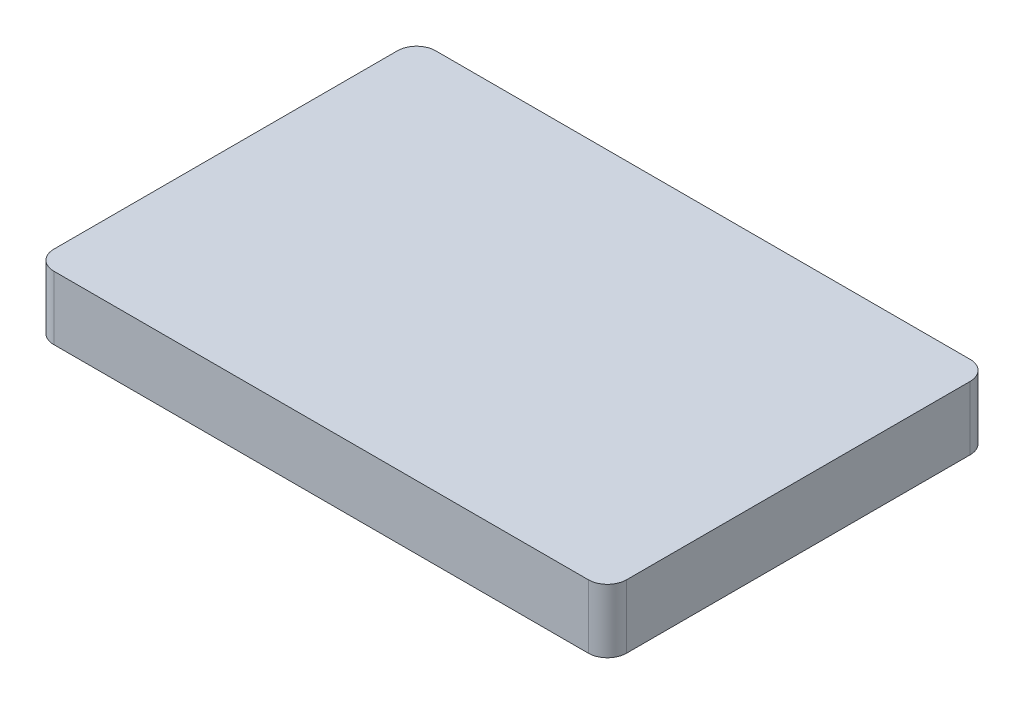
SolidWorks part; units mm, degrees
ref_plane "前视基准面" through (0, 0, 0) normal (0, 0, 1) x (1, 0, 0)
ref_plane "上视基准面" through (0, 0, 0) normal (0, 1, 0) x (1, 0, 0)
ref_plane "右视基准面" through (0, 0, 0) normal (1, 0, 0) x (0, 0, -1)
sketch "草图1" plane through (0, 0, 0) normal (0, 1, 0) x (1, 0, 0)
  line L1 (-45, 30) -> (45, 30)
  line L2 (-45, 30) -> (-45, -30)
  line L3 (-45, -30) -> (45, -30)
  line L4 (45, 30) -> (45, -30)
  line L5 (-45, 30) -> (45, -30) construction
  line L6 (-45, -30) -> (45, 30) construction
  point P0 (0, 0)
  dimension "D1" = 60
  dimension "D2" = 90
extrude "凸台-拉伸1" add sketch "草图1" along normal blind 10
fillet "圆角1" radius 3 4 edges at (-45, 5, -30) (45, 5, -30) (45, 5, 30) (-45, 5, 30)
